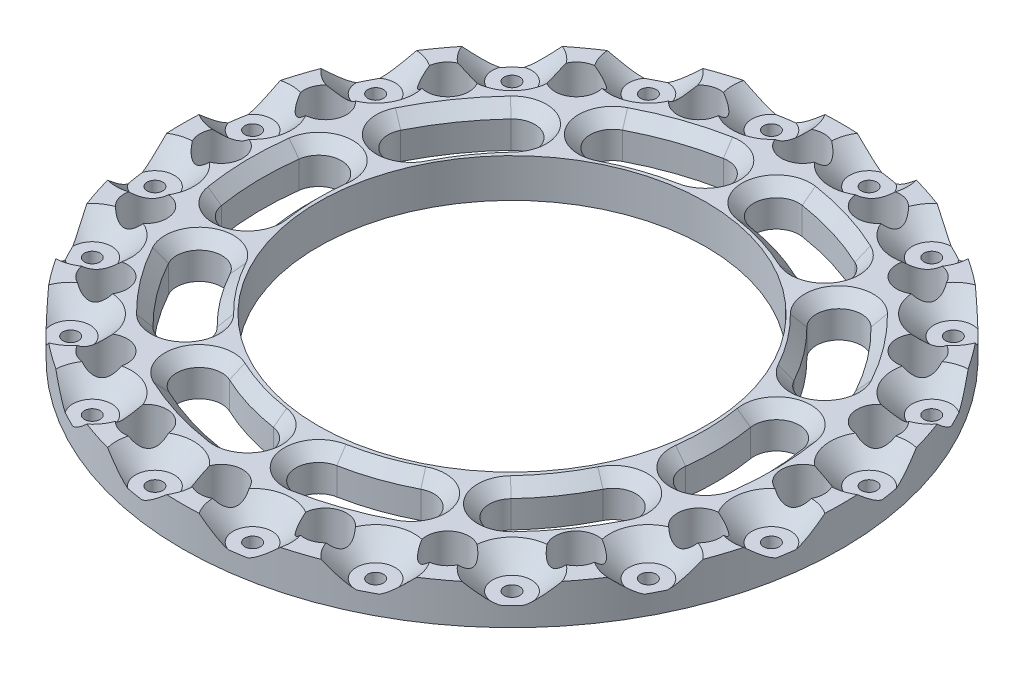
SolidWorks part; units mm, degrees
ref_plane "Front Plane" through (0, 0, 0) normal (0, 0, 1) x (1, 0, 0)
ref_plane "Top Plane" through (0, 0, 0) normal (0, 1, 0) x (1, 0, 0)
ref_plane "Right Plane" through (0, 0, 0) normal (1, 0, 0) x (0, 0, -1)
sketch "Sketch1" plane through (0, 0, 0) normal (0, 1, 0) x (1, 0, 0)
  circle A1 centre (-75, 0) radius 5.5
  circle A2 centre (-71.3292, 23.1763) radius 5.5
  circle A3 centre (-60.6763, 44.0839) radius 5.5
  circle A4 centre (-44.0839, 60.6763) radius 5.5
  circle A5 centre (-23.1763, 71.3292) radius 5.5
  circle A6 centre (0, 75) radius 5.5
  circle A7 centre (23.1763, 71.3292) radius 5.5
  circle A8 centre (44.0839, 60.6763) radius 5.5
  circle A9 centre (60.6763, 44.0839) radius 5.5
  circle A10 centre (71.3292, 23.1763) radius 5.5
  circle A11 centre (75, 0) radius 5.5
  circle A12 centre (71.3292, -23.1763) radius 5.5
  circle A13 centre (60.6763, -44.0839) radius 5.5
  circle A14 centre (44.0839, -60.6763) radius 5.5
  circle A15 centre (23.1763, -71.3292) radius 5.5
  circle A16 centre (0, -75) radius 5.5
  circle A17 centre (-23.1763, -71.3292) radius 5.5
  circle A18 centre (-44.0839, -60.6763) radius 5.5
  circle A19 centre (-60.6763, -44.0839) radius 5.5
  circle A20 centre (-71.3292, -23.1763) radius 5.5
  circle A22 centre (0, 0) radius 85
  circle A24 centre (0, 0) radius 50
  point P46 (0, 0)
  point P80 (0, 0)
  dimension "D1" = 20
extrude "Boss-Extrude4" add sketch "Sketch1" along normal blind 10
sketch "Sketch4" plane through (0, 10, 0) normal (0, 1, 0) x (1, 0, 0)
  line L0 (-85, 0) -> (-75, 0)
  line L1 (0, 0) -> (-75, 0)
  line L2 (0, 0) -> (-71.3292, 23.1763)
  line L3 (0, 0) -> (-79.5089, 12.593)
  circle A0 centre (0, 0) radius 85
  circle A1 centre (0, 0) radius 75
  circle A2 centre (0, 0) radius 80.5
  circle A3 centre (-79.5089, 12.593) radius 2
  circle A4 centre (-71.726, 36.5462) radius 2
  circle A5 centre (-56.9221, 56.9221) radius 2
  circle A6 centre (-36.5462, 71.726) radius 2
  circle A7 centre (-12.593, 79.5089) radius 2
  circle A8 centre (12.593, 79.5089) radius 2
  circle A9 centre (36.5462, 71.726) radius 2
  circle A10 centre (56.9221, 56.9221) radius 2
  circle A11 centre (71.726, 36.5462) radius 2
  circle A12 centre (79.5089, 12.593) radius 2
  circle A13 centre (79.5089, -12.593) radius 2
  circle A14 centre (71.726, -36.5462) radius 2
  circle A15 centre (56.9221, -56.9221) radius 2
  circle A16 centre (36.5462, -71.726) radius 2
  circle A17 centre (12.593, -79.5089) radius 2
  circle A18 centre (-12.593, -79.5089) radius 2
  circle A19 centre (-36.5462, -71.726) radius 2
  circle A20 centre (-56.9221, -56.9221) radius 2
  circle A21 centre (-71.726, -36.5462) radius 2
  circle A22 centre (-79.5089, -12.593) radius 2
  point P53 (0, 0)
  dimension "D2" = 20
  dimension "D1" = 9
extrude "Cut-Extrude5" cut sketch "Sketch4" against normal blind 15 contours A3 | A4 | A5 | A6 | A7 | A8 | A9 | A10 | A11 | A12 | A13 | A14 | A15 | A16 | A22 | A21 | A20 | A19 | A18 | A17
sketch "Sketch5" plane through (0, 10, 0) normal (0, 1, 0) x (1, 0, 0)
  circle A0 centre (-71.726, -36.5462) radius 5
  circle A1 centre (-79.5089, -12.593) radius 5
  circle A2 centre (-79.5089, 12.593) radius 5
  circle A3 centre (-71.726, 36.5462) radius 5
  circle A4 centre (-56.9221, 56.9221) radius 5
  circle A5 centre (-36.5462, 71.726) radius 5
  circle A6 centre (-12.593, 79.5089) radius 5
  circle A7 centre (12.593, 79.5089) radius 5
  circle A8 centre (36.5462, 71.726) radius 5
  circle A9 centre (56.9221, 56.9221) radius 5
  circle A10 centre (71.726, 36.5462) radius 5
  circle A11 centre (79.5089, 12.593) radius 5
  circle A12 centre (79.5089, -12.593) radius 5
  circle A13 centre (71.726, -36.5462) radius 5
  circle A14 centre (56.9221, -56.9221) radius 5
  circle A15 centre (36.5462, -71.726) radius 5
  circle A16 centre (12.593, -79.5089) radius 5
  circle A17 centre (-12.593, -79.5089) radius 5
  circle A18 centre (-36.5462, -71.726) radius 5
  circle A19 centre (-56.9221, -56.9221) radius 5
  point P44 (0, 0)
  dimension "D1" = 20
extrude "Cut-Extrude6" cut sketch "Sketch5" against normal blind 5
chamfer "Chamfer4" distance 5 angle 45 20 edges at (-34.2763, 10, -67.271) (-11.8108, 10, -74.5705) (11.8108, 10, -74.5705) (34.2763, 10, -67.271) (53.3866, 10, -53.3866) (67.271, 10, -34.2763) (74.5705, 10, -11.8108) (74.5705, 10, 11.8108) (67.271, 10, 34.2763) (53.3866, 10, 53.3866) (34.2763, 10, 67.271) (11.8108, 10, 74.5705) (-11.8108, 10, 74.5705) (-34.2763, 10, 67.271) (-53.3866, 10, 53.3866) (-67.271, 10, 34.2763) (-74.5705, 10, 11.8108) (-53.3866, 10, -53.3866) (-67.271, 10, -34.2763) (-74.5705, 10, -11.8108)
sketch "Sketch6" plane through (0, 10, 0) normal (0, 1, 0) x (1, 0, 0)
  line L0 (-69.5, 0) -> (-50, 0)
  line L5 (-68.4808, -10.8738) -> (-49.3051, -7.8367)
  line L6 (-68.565, 10.8572) -> (-49.9206, 7.9043)
  circle A0 centre (0, 0) radius 69.5
  circle A1 centre (0, 0) radius 50
  arc A2 (-58.8929, -9.3553) -> (-59.2428, 9.3807) centre (4.9184, 1.2076) cw construction
  arc A3 (-65.0505, 10.1205) -> (-64.6689, -10.3114) centre (4.9184, 1.2076) ccw
  arc A4 (-53.4351, 8.6409) -> (-53.1169, -8.3991) centre (4.9184, 1.2076) ccw
  arc A5 (-53.4351, 8.6409) -> (-65.0505, 10.1205) centre (-59.2428, 9.3807) ccw
  arc A6 (-64.6689, -10.3114) -> (-53.1169, -8.3991) centre (-58.8929, -9.3553) ccw
  arc A7 (-53.1443, 27.0478) -> (-42.4146, 42.4112) centre (4.6889, -1.914) cw construction
  arc A8 (-46.6782, 46.4234) -> (-58.3791, 29.6694) centre (4.6889, -1.914) ccw
  arc A9 (-38.1509, 38.399) -> (-47.9094, 24.4263) centre (4.6889, -1.914) ccw
  arc A10 (-38.1509, 38.399) -> (-46.6782, 46.4234) centre (-42.4146, 42.4112) ccw
  arc A11 (-58.3791, 29.6694) -> (-47.9094, 24.4263) centre (-53.1443, 27.0478) ccw
  arc A12 (-27.0963, 53.1196) -> (-9.3854, 59.2421) centre (2.6684, -4.3045) cw construction
  arc A13 (-10.4765, 64.9941) -> (-29.7905, 58.3174) centre (2.6684, -4.3045) ccw
  arc A14 (-8.2943, 53.49) -> (-24.4021, 47.9217) centre (2.6684, -4.3045) ccw
  arc A15 (-8.2943, 53.49) -> (-10.4765, 64.9941) centre (-9.3854, 59.2421) ccw
  arc A16 (-29.7905, 58.3174) -> (-24.4021, 47.9217) centre (-27.0963, 53.1196) ccw
  arc A17 (9.3015, 58.9014) -> (27.2286, 53.4445) centre (-0.3713, -5.0509) cw construction
  arc A18 (29.7269, 58.7393) -> (10.1771, 64.6902) centre (-0.3713, -5.0509) ccw
  arc A19 (24.7304, 48.1496) -> (8.426, 53.1127) centre (-0.3713, -5.0509) ccw
  arc A20 (24.7304, 48.1496) -> (29.7269, 58.7393) centre (27.2286, 53.4445) ccw
  arc A21 (10.1771, 64.6902) -> (8.426, 53.1127) centre (9.3015, 58.9014) ccw
  arc A22 (42.1465, 42.185) -> (53.4423, 27.2329) centre (-3.2692, -3.868) cw construction
  arc A23 (58.5757, 30.048) -> (46.2574, 46.3535) centre (-3.2692, -3.868) ccw
  arc A24 (48.3089, 24.4177) -> (38.0356, 38.0164) centre (-3.2692, -3.868) ccw
  arc A25 (48.3089, 24.4177) -> (58.5757, 30.048) centre (53.4423, 27.2329) ccw
  arc A26 (46.2574, 46.3535) -> (38.0356, 38.0164) centre (42.1465, 42.185) ccw
  arc A27 (58.8929, 9.3553) -> (59.2428, -9.3807) centre (-4.9184, -1.2076) cw construction
  arc A28 (65.0505, -10.1205) -> (64.6689, 10.3114) centre (-4.9184, -1.2076) ccw
  arc A29 (53.4351, -8.6409) -> (53.1169, 8.3991) centre (-4.9184, -1.2076) ccw
  arc A30 (53.4351, -8.6409) -> (65.0505, -10.1205) centre (59.2428, -9.3807) ccw
  arc A31 (64.6689, 10.3114) -> (53.1169, 8.3991) centre (58.8929, 9.3553) ccw
  arc A32 (53.1443, -27.0478) -> (42.4146, -42.4112) centre (-4.6889, 1.914) cw construction
  arc A33 (46.6782, -46.4234) -> (58.3791, -29.6694) centre (-4.6889, 1.914) ccw
  arc A34 (38.1509, -38.399) -> (47.9094, -24.4263) centre (-4.6889, 1.914) ccw
  arc A35 (38.1509, -38.399) -> (46.6782, -46.4234) centre (42.4146, -42.4112) ccw
  arc A36 (58.3791, -29.6694) -> (47.9094, -24.4263) centre (53.1443, -27.0478) ccw
  arc A37 (27.0963, -53.1196) -> (9.3854, -59.2421) centre (-2.6684, 4.3045) cw construction
  arc A38 (10.4765, -64.9941) -> (29.7905, -58.3174) centre (-2.6684, 4.3045) ccw
  arc A39 (8.2943, -53.49) -> (24.4021, -47.9217) centre (-2.6684, 4.3045) ccw
  arc A40 (8.2943, -53.49) -> (10.4765, -64.9941) centre (9.3854, -59.2421) ccw
  arc A41 (29.7905, -58.3174) -> (24.4021, -47.9217) centre (27.0963, -53.1196) ccw
  arc A42 (-9.3015, -58.9014) -> (-27.2286, -53.4445) centre (0.3713, 5.0509) cw construction
  arc A43 (-29.7269, -58.7393) -> (-10.1771, -64.6902) centre (0.3713, 5.0509) ccw
  arc A44 (-24.7304, -48.1496) -> (-8.426, -53.1127) centre (0.3713, 5.0509) ccw
  arc A45 (-24.7304, -48.1496) -> (-29.7269, -58.7393) centre (-27.2286, -53.4445) ccw
  arc A46 (-10.1771, -64.6902) -> (-8.426, -53.1127) centre (-9.3015, -58.9014) ccw
  arc A47 (-42.1465, -42.185) -> (-53.4423, -27.2329) centre (3.2692, 3.868) cw construction
  arc A48 (-58.5757, -30.048) -> (-46.2574, -46.3535) centre (3.2692, 3.868) ccw
  arc A49 (-48.3089, -24.4177) -> (-38.0356, -38.0164) centre (3.2692, 3.868) ccw
  arc A50 (-48.3089, -24.4177) -> (-58.5757, -30.048) centre (-53.4423, -27.2329) ccw
  arc A51 (-46.2574, -46.3535) -> (-38.0356, -38.0164) centre (-42.1465, -42.185) ccw
  point P6 (-59.2428, 9.3807)
  point P8 (-59.75, 0)
  point P9 (-58.8929, -9.3553)
  point P16 (-59.75, 0)
  point P26 (-48.3388, 35.1202)
  point P34 (-18.4638, 56.8256)
  point P42 (18.4638, 56.8256)
  point P50 (48.3388, 35.1202)
  point P58 (59.75, 0)
  point P66 (48.3388, -35.1202)
  point P74 (18.4638, -56.8256)
  point P82 (-18.4638, -56.8256)
  point P90 (-48.3388, -35.1202)
  point P95 (0, 0)
  dimension "D1" = 10
extrude "Cut-Extrude7" cut sketch "Sketch6" against normal blind 15 contours L5 A6 A4 L0 A3 | L6 A5 A3 L0 A4 | A4 A5 L6 | A3 A6 L5 | A8 A11 A9 A10 | A13 A16 A14 A15 | A18 A21 A19 A20 | A23 A26 A24 A25 | A28 A31 A29 A30 | A33 A36 A34 A35 | A38 A41 A39 A40 | A43 A46 A44 A45 | A48 A51 A49 A50 region at (-59.8002, 10, -4.7115) region at (-59.6249, 10, 4.703) region at (-58.5042, 10, 11.8094) region at (-58.8541, 10, -11.8349) region at (-48.0298, 10, -34.9044) region at (-18.3406, 10, -56.4694) region at (18.354, 10, -56.4651) region at (48.038, 10, -34.893) region at (59.3732, 10, 0.007) region at (48.0298, 10, 34.9044) region at (18.3406, 10, 56.4694) region at (-18.354, 10, 56.4651) region at (-48.038, 10, 34.893)
chamfer "Chamfer5" distance 3 angle 45 40 edges at (-37.9779, 10, 46.2959) (-43.6674, 10, 31.5911) (-53.0102, 10, 38.6493) (-56.2575, 10, 22.0995) (-3.5128, 10, 59.777) (-16.7589, 10, 51.2248) (-20.1687, 10, 62.4265) (-32.5235, 10, 50.9462) (3.6334, 10, 60.3331) (20.3766, 10, 62.3589) (16.5509, 10, 51.2923) (32.2941, 10, 50.4254) (55.7658, 10, 21.8129) (43.5389, 10, 31.768) (53.1387, 10, 38.4724) (38.4024, 10, 46.6749) (58.503, 10, 15.1884) (65.6036, 10, -0.1093) (53.8964, 10, 0.1093) (57.9368, 10, -15.1313) (56.2575, 10, -22.0995) (53.0102, 10, -38.6493) (43.6674, 10, -31.5911) (37.9779, 10, -46.2959) (32.5235, 10, -50.9462) (20.1687, 10, -62.4265) (16.7589, 10, -51.2248) (3.5128, 10, -59.777) (-3.6334, 10, -60.3331) (-20.3766, 10, -62.3589) (-16.5509, 10, -51.2923) (-32.2941, 10, -50.4254) (-57.9368, 10, 15.1313) (-53.8964, 10, -0.1093) (-65.6036, 10, 0.1093) (-58.503, 10, -15.1884) (-38.4024, 10, -46.6749) (-53.1387, 10, -38.4724) (-43.5389, 10, -31.768) (-55.7658, 10, -21.8129)
